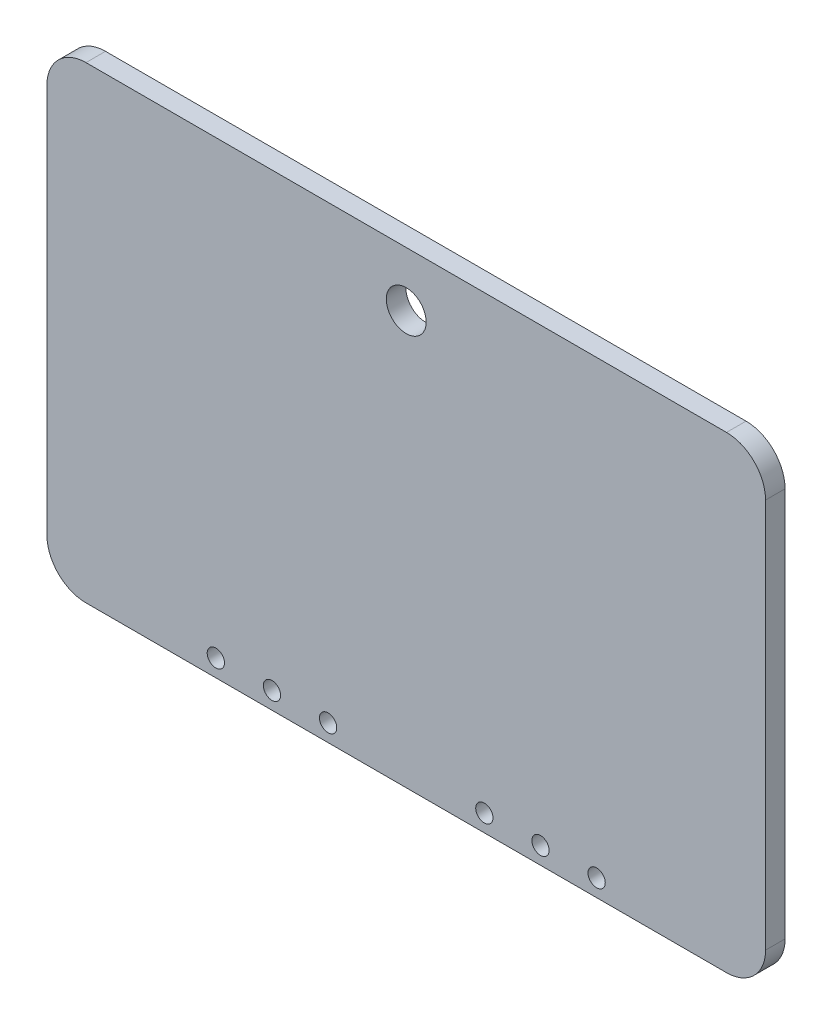
SolidWorks part; units mm, degrees
material "Acrylic (Medium-high impact)"
ref_plane "Front Plane" through (0, 0, 0) normal (0, 0, 1) x (1, 0, 0)
ref_plane "Top Plane" through (0, 0, 0) normal (0, 1, 0) x (1, 0, 0)
ref_plane "Right Plane" through (0, 0, 0) normal (1, 0, 0) x (0, 0, -1)
sketch "Sketch1" plane through (0, 0, 0) normal (0, 0, 1) x (1, 0, 0)
  line L1 (233.68, 152.146) -> (0, 152.146)
  line L2 (233.68, 152.146) -> (233.68, 0)
  line L3 (233.68, 0) -> (0, 0)
  line L4 (0, 152.146) -> (0, 0)
  line L5 (233.68, 152.146) -> (0, 0) construction
  line L6 (233.68, 0) -> (0, 152.146) construction
  point P0 (116.84, 76.073)
  dimension "D1" = 152.146
  dimension "D2" = 233.68
extrude "Boss-Extrude1" add sketch "Sketch1" along normal blind 6.35
hole_wizard "#10 Clearance Hole1" positions "Sketch6" profile "Sketch7" hole size "#10" standard "ANSI Inch" end condition through all
sketch "Sketch6" plane through (0, 0, 6.35) normal (0, 0, 1) x (1, 0, 0)
  line L2 (0, 0) -> (233.68, 0) construction
  line L3 (91.44, 5.588) -> (142.24, 5.588) construction
  line L5 (116.84, 0) -> (116.84, 5.588) construction
  line L6 (54.9275, 5.588) -> (91.44, 5.588) construction
  line L9 (142.24, 5.588) -> (178.7525, 5.588) construction
  point P0 (54.9275, 5.588)
  point P11 (91.44, 5.588)
  point P13 (142.24, 5.588)
  point P15 (178.7525, 5.588)
  point P29 (73.1837, 5.588)
  point P31 (160.4963, 5.588)
  point P45 (73.1837, 5.588)
  point P47 (160.4963, 5.588)
  dimension "D1" = 36.5125
  dimension "D2" = 5.588
  dimension "D5" = 50.8
sketch "Sketch7" plane through (54.9275, 5.588, 6.35) normal (1, 0, 0) x (0, -1, 0)
  line L0 (0, 0) -> (0, 6.35)
  line L1 (0, 6.35) -> (2.8067, 6.35)
  line L2 (2.8067, 6.35) -> (2.8067, 0)
  line L5 (2.8067, 0) -> (0, 0)
  line L11 (0, -6.35) -> (0, 107.95) construction
  dimension "Thru Hole Dia." = 5.6134
  dimension "Thru Hole Depth" = 6.35
sketch "Sketch8" plane through (0, 0, 6.35) normal (0, 0, 1) x (1, 0, 0)
  line L0 (0, 0) -> (233.68, 0) construction
  line L1 (233.68, 152.146) -> (0, 152.146) construction
  circle A0 centre (116.84, 134.366) radius 6.477
  point P6 (116.84, 0)
  dimension "D1" = 12.954
  dimension "D2" = 17.78
extrude "Cut-Extrude1" cut sketch "Sketch8" against normal through all
fillet "Fillet1" radius 12.7 4 edges at (233.68, 0, 3.175) (233.68, 152.146, 3.175) (0, 152.146, 3.175) (0, 0, 3.175)
